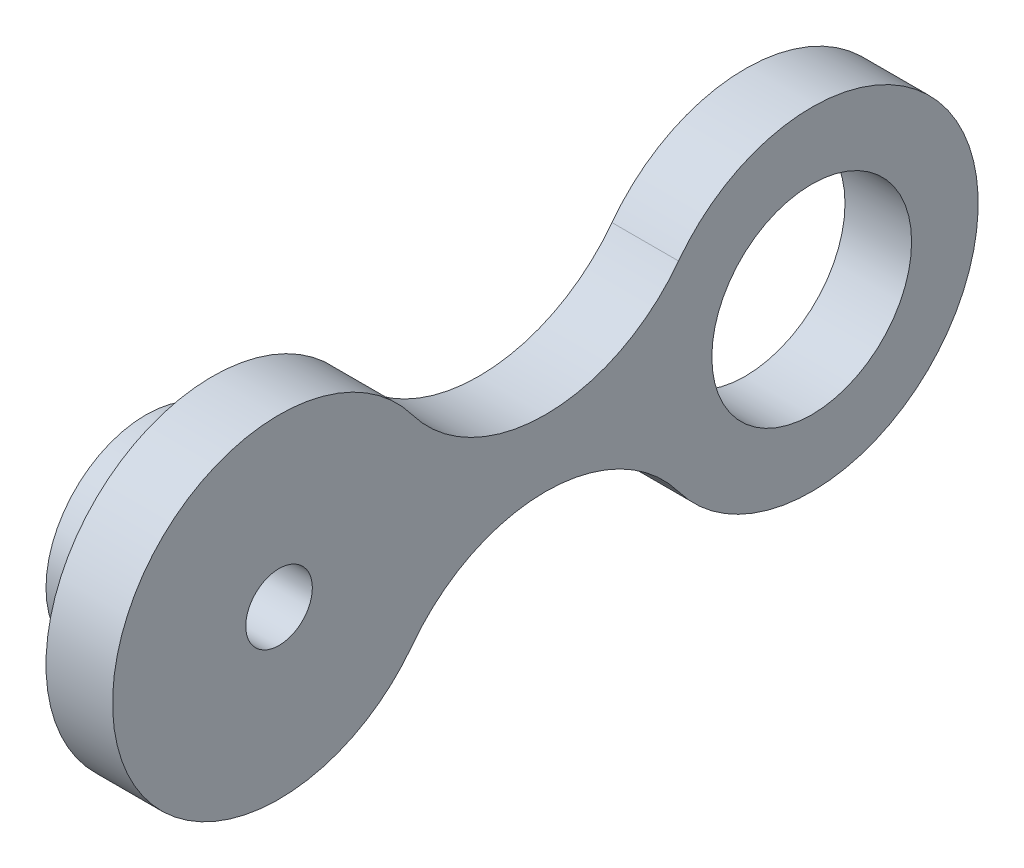
SolidWorks part; units mm, degrees
ref_plane "Front Plane" through (0, 0, 0) normal (0, 0, 1) x (1, 0, 0)
ref_plane "Top Plane" through (0, 0, 0) normal (0, 1, 0) x (1, 0, 0)
ref_plane "Right Plane" through (0, 0, 0) normal (1, 0, 0) x (0, 0, -1)
sketch "Sketch1" plane through (0, 0, 0) normal (1, 0, 0) x (0, 0, -1)
  line L0 (0, 0) -> (80, 0) construction
  circle A0 centre (0, 0) radius 25
  circle A1 centre (80, 0) radius 25
  circle A2 centre (0, 0) radius 15
  circle A3 centre (80, 0) radius 15
  arc A4 (20, -15) -> (60, -15) centre (40, -30) cw
  arc A5 (20, 15) -> (60, 15) centre (40, 30) ccw
  point P15 (40, -5)
  point P16 (40, 5)
  dimension "D1" = 50
  dimension "D2" = 50
  dimension "D5" = 10
  dimension "D6" = 10
  dimension "D3" = 80
  dimension "D4" = 10
extrude "Boss-Extrude1" add sketch "Sketch1" along normal blind 10 contours A2 A0 | L0 A0 A4 A1 | A0 L0 A1 A5 | A1 A3 region at (0, -7.6821, -23.0463) region at (0, 3.9551, -40) region at (0, -3.9551, -40) region at (0, 7.6821, -56.9537)
sketch "Sketch2" plane through (0, 0, 0) normal (-1, 0, 0) x (0, 0, 1)
  circle A0 centre (0, 0) radius 15
extrude "Boss-Extrude2" add sketch "Sketch2" against normal blind 10
sketch "Sketch3" plane through (0, 0, 0) normal (-1, 0, 0) x (0, 0, 1)
  circle A0 centre (0, 0) radius 15
  arc A1 (-20, -15) -> (-20, 15) centre (0, 0) ccw construction
  dimension "D1" = 10
extrude "Boss-Extrude3" add sketch "Sketch3" along normal blind 10
sketch "Sketch4" plane through (-10, 0, 0) normal (-1, 0, 0) x (0, 0, 1)
  circle A2 centre (0, 0) radius 5
  circle A3 centre (0, 0) radius 5
  dimension "D1" = 10
extrude "Cut-Extrude1" cut sketch "Sketch4" against normal blind 36
ref_axis "Axis1" through (-10, 0, 0) along (1, 0, 0)
ref_plane "Plane1" through (-5, 0, 0) normal (-1, 0, 0) x (0, 0, 1)
ref_axis "Axis2" through (10, 0, -80) along (-1, 0, 0)
ref_plane "Plane2" through (5, 0, 0) normal (-1, 0, 0) x (0, 0, 1)
ref_point "Point1"
ref_point "Point2"
